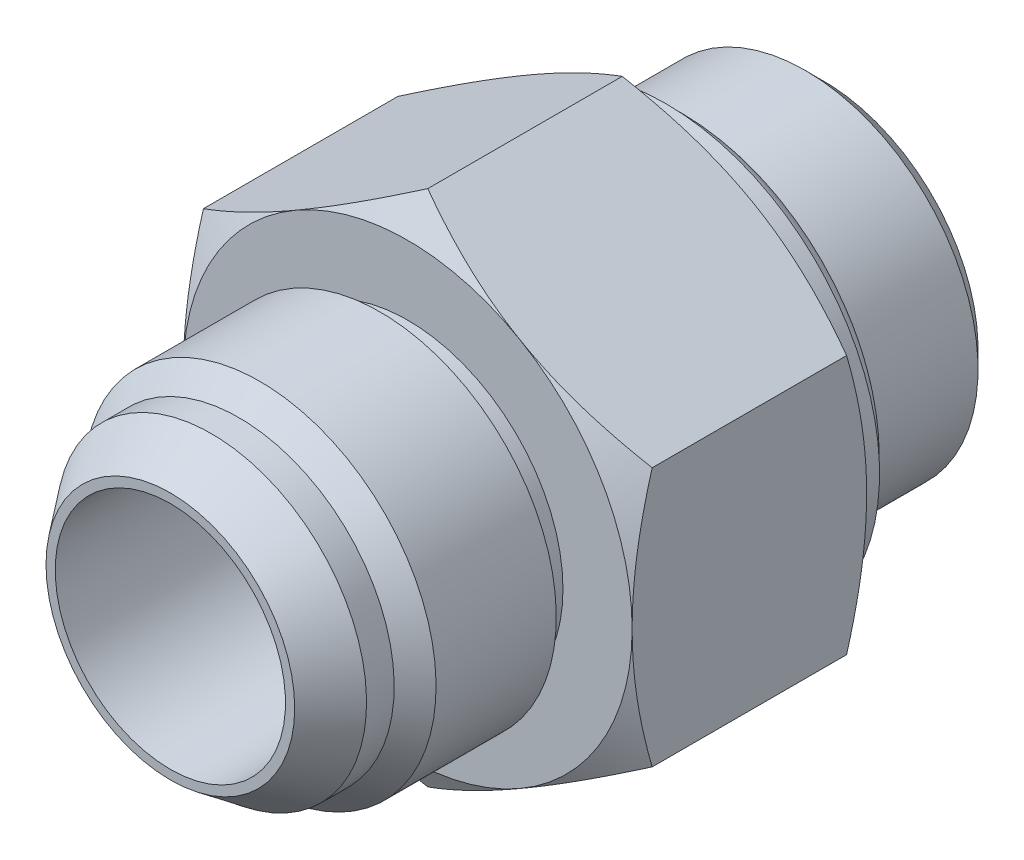
SolidWorks part; units mm, degrees
material "AISI 316 Stainless Steel Sheet (SS)"
ref_plane "Front Plane" through (0, 0, 0) normal (0, 0, 1) x (1, 0, 0)
ref_plane "Top Plane" through (0, 0, 0) normal (0, 1, 0) x (1, 0, 0)
ref_plane "Right Plane" through (0, 0, 0) normal (1, 0, 0) x (0, 0, -1)
sketch "Sketch1" plane through (0, 0, 0) normal (1, 0, 0) x (0, 0, -1)
  line L0 (-25.0031, 0) -> (25.0031, 0) construction
  line L1 (11.1423, 13.2207) -> (11.1423, -13.2207) construction
  line L2 (-6.819, 13.4937) -> (-6.819, -13.4938) construction
  line L3 (11.1423, 13.2207) -> (25.0031, 13.2207) construction
  line L4 (24.8897, 13.4385) -> (26.704, 13.4385) construction
  line L5 (24.8897, 13.4385) -> (25.7969, 11.6959) construction
  line L6 (25.7969, 11.6959) -> (26.704, 13.4385) construction
  line L7 (25.7969, 13.4385) -> (25.7969, 13.2207) construction
  line L8 (25.7969, 11.6959) -> (25.7969, 11.9137) construction
  line L9 (25.6835, 11.9137) -> (25.9103, 11.9137) construction
  line L10 (25.0031, 13.2207) -> (26.5906, 13.2207) construction
  line L11 (26.6473, 13.3296) -> (24.9464, 13.3296) construction
  line L12 (-26.9875, 13.7229) -> (-25.9292, 11.8898)
  line L13 (-26.9875, 13.7229) -> (-24.8708, 13.7229)
  line L14 (-24.8708, 13.7229) -> (-25.9292, 11.8898)
  line L15 (-25.9292, 13.7229) -> (-25.9292, 13.4937) construction
  line L16 (-25.9292, 11.8898) -> (-25.9292, 12.1189) construction
  line L17 (-26.0615, 12.1189) -> (-25.7969, 12.1189) construction
  line L18 (-26.8552, 13.4937) -> (-25.0031, 13.4937) construction
  line L19 (-26.9214, 13.6083) -> (-24.937, 13.6083) construction
  line L20 (11.1423, 17.1869) -> (11.1423, -17.1869) construction
  line L21 (11.1423, -13.2207) -> (25.0031, -13.2207) construction
  point P2 (11.1423, 0)
  point P4 (-6.819, 0)
  point P27 (25.7969, 13.3296)
  point P32 (-17.5948, -13.4937)
  point P33 (18.6531, -13.2207)
  point P40 (-25.9292, 13.6083)
  dimension "Length" = 50.0062
  dimension "PTL" = 13.8608
  dimension "PD" = 26.4414
  dimension "TD" = 26.9875
  dimension "D1" = 55
  dimension "P Pitch" = 1.8143
  dimension "D2" = 0.2268
  dimension "T Pitch" = 2.1167
  dimension "D3" = 0.2646
  dimension "D4" = 18.1841
  dimension "D5" = 34.3738
  dimension "D6" = 7.4083
  dimension "D7" = 6.35
sketch "Sketch2" plane through (0, 0, 0) normal (0, 0, 1) x (1, 0, 0)
  line L0 (0, 13.2207) -> (0, -13.2207) construction
  line L1 (0, 19.8457) -> (-17.1869, 9.9229)
  line L2 (-17.1869, 9.9229) -> (-17.1869, -9.9229)
  line L3 (-17.1869, -9.9229) -> (0, -19.8457)
  line L4 (0, -19.8457) -> (17.1869, -9.9229)
  line L5 (17.1869, -9.9229) -> (17.1869, 9.9229)
  line L6 (17.1869, 9.9229) -> (0, 19.8457)
  circle A0 centre (0, 0) radius 17.1869 construction
extrude "Boss-Extrude1" add sketch "Sketch2" along normal up to vertex (6.819 mm away) from vertex up to point (0, 0, 6.819) starting at point (0, 0, -11.1423)
sketch "Sketch3" plane through (0, 0, 6.819) normal (0, 0, 1) x (1, 0, 0)
  circle A0 centre (0, 0) radius 17.1869 construction
  circle A1 centre (0, 0) radius 17.1869
extrude "Cut-Extrude1" cut sketch "Sketch3" against normal through all draft 60 flip side to cut
sketch "Sketch4" plane through (0, 0, -11.1423) normal (0, 0, -1) x (-1, 0, 0)
  circle A0 centre (0, 0) radius 17.1869 construction
  circle A1 centre (0, 0) radius 17.1869
extrude "Cut-Extrude2" cut sketch "Sketch4" against normal through all draft 60 flip side to cut
sketch "Sketch5" plane through (0, 0, 0) normal (1, 0, 0) x (0, 0, -1)
  line L0 (-25.0031, 0) -> (-25.0031, 9.525)
  line L1 (-25.0031, 9.525) -> (-21.8649, 11.8898)
  line L2 (-21.8649, 11.8898) -> (-19.7483, 11.8898)
  line L3 (-18.1443, 13.4937) -> (-8.9357, 13.4937)
  line L4 (-8.9357, 13.4937) -> (-8.0097, 11.8898)
  line L5 (2.1617, 13.2207) -> (2.1617, 19.8457) construction
  line L6 (23.6424, 13.2207) -> (25.0031, 11.86)
  line L7 (-5.284, 19.8457) -> (9.6073, 19.8457) construction
  line L8 (11.1423, 13.2207) -> (25.0031, 13.2207) construction
  line L9 (25.0031, 11.86) -> (25.0031, 0)
  line L10 (-25.0031, 0) -> (25.0031, 0) construction
  line L11 (23.6424, 13.2207) -> (13.9652, 13.2207)
  line L12 (-8.0097, 11.8898) -> (2.1617, 11.8898)
  line L13 (2.1617, 11.8898) -> (2.1617, 13.2207)
  line L14 (11.1423, 11.6959) -> (13.4102, 11.6959)
  line L15 (-6.819, 13.4937) -> (-6.819, -13.4938) construction
  line L16 (-19.7483, 11.8898) -> (-18.1443, 13.4937)
  line L17 (-25.0031, 0) -> (25.0031, 0) construction
  line L18 (-25.0031, 0) -> (25.0031, 0)
  line L19 (13.4102, 11.6959) -> (13.9652, 13.2207)
  line L20 (11.1423, 11.6959) -> (11.1423, 13.2207)
  line L21 (11.1423, 13.2207) -> (2.1617, 13.2207)
  line L22 (-25.0031, 0) -> (-29.7627, 0) construction
  dimension "D1" = 37
  dimension "D2" = 2.1167
  dimension "D3" = 60
  dimension "D4" = 45
  dimension "D5" = 2.1167
  dimension "D7" = 45
  dimension "D8" = 1.3607
  dimension "D9" = 2.2679
  dimension "D10" = 70
  dimension "D11" = 5.491
  dimension "TOD" = 19.05
revolve "Revolve1" add sketch "Sketch5" angle 360 about L18
sketch "Sketch6" plane through (0, 0, 0) normal (1, 0, 0) x (0, 0, -1)
  line L0 (-25.0031, 8.8194) -> (11.1423, 8.8194)
  line L1 (25.0031, 9.5188) -> (11.1423, 9.5188)
  line L2 (11.1423, 13.2207) -> (11.1423, -13.2207) construction
  line L3 (11.1423, 9.5188) -> (11.1423, 8.8194)
  line L4 (25.0031, -13.2207) -> (25.0031, 13.2207) construction
  line L5 (-25.0031, 9.525) -> (-25.0031, -9.525) construction
  line L6 (-25.0031, 8.8194) -> (-25.0031, 0)
  line L7 (25.0031, 9.5188) -> (25.0031, 0)
  line L8 (25.0031, 0) -> (-25.0031, 0)
  dimension "D1" = 2.1771
  dimension "D2" = 0.7056
revolve "Cut-Revolve1" cut sketch "Sketch6" angle 360 about L8
sketch "Sketch11" plane through (0, 0, 0) normal (1, 0, 0) x (0, 0, -1)
  line L6 (11.1423, 11.6959) -> (11.1423, 16.3633)
  line L8 (11.1423, 16.3633) -> (12.9566, 16.3633)
  line L9 (12.9566, 16.3633) -> (12.9566, 15.6624)
  line L10 (11.1423, 11.6959) -> (12.9566, 11.6959)
  line L11 (12.9566, 12.3967) -> (12.9566, 11.6959)
  arc A0 (12.9566, 12.3967) -> (12.9566, 15.6624) centre (12.9566, 14.0296) ccw
  point P17 (14.5895, 14.0296)
  dimension "D1" = 1.8143
  dimension "D2" = 1.6329
  dimension "D3" = 4.6673
revolve "Revolve2" add sketch "Sketch11" angle 360 about L0
split "Split1" [suppressed] bodies to split 108
sketch "Sketch7" [suppressed] plane through (0, 0, 25.0031) normal (0, 0, 1) x (1, 0, 0)
  circle A0 centre (0, 0) radius 13.4938
  circle A1 centre (0, 0) radius 13.4937 construction
curve "Helix/Spiral1" [suppressed] pitch 2.1167 height 20.3008 turns 9.5909
sketch "Sketch8" [suppressed] plane through (0, 0, 0) normal (1, 0, 0) x (0, 0, -1)
  line L0 (-24.937, 13.6083) -> (-26.9214, 13.6083)
  line L1 (-26.9214, 13.6083) -> (-26.0615, 12.1189)
  line L2 (-26.0615, 12.1189) -> (-25.7969, 12.1189)
  line L3 (-25.7969, 12.1189) -> (-24.937, 13.6083)
sweep "Cut-Sweep1" [suppressed] cut profiles "Sketch8" path "Helix/Spiral1"
sketch "Sketch9" [suppressed] plane through (0, 0, -25.0031) normal (0, 0, -1) x (-1, 0, 0)
  circle A0 centre (0, 0) radius 13.2207 construction
  circle A1 centre (0, 0) radius 13.2207
curve "Helix/Spiral2" [suppressed]
sketch "Sketch10" [suppressed] plane through (0, 0, 0) normal (1, 0, 0) x (0, 0, -1)
  line L2 (25.7969, 11.6959) -> (25.7969, 11.9137) construction
  line L3 (25.7969, 11.6959) -> (26.704, 13.4385) construction
  line L14 (24.8897, 13.4385) -> (26.6473, 13.3296)
  line L15 (24.8897, 13.4385) -> (25.6311, 12.0143)
  line L16 (25.9626, 12.0143) -> (26.6473, 13.3296)
  line L17 (24.8897, 13.4385) -> (25.7969, 11.6959) construction
  arc A0 (25.6311, 12.0143) -> (25.9626, 12.0143) centre (25.7969, 12.1006) ccw
  dimension "D1" = 0.1869
sweep "Cut-Sweep2" [suppressed] cut profiles "Sketch10" path "Helix/Spiral2"
fillet "Fillet1" [suppressed] radius 0.1682
combine bodies "Combine1" [suppressed] operation type add bodies to combine 111 112 119
ref_axis "Center Axis 1" through (0, 0, 22.2913) along (0, 0, -1)
ref_plane "Contact Plane 1" through (0, 0, 6.819) normal (0, 0, 1) x (1, 0, 0)
ref_plane "Contact Plane 2" through (0, 0, -11.1423) normal (0, 0, -1) x (-1, 0, 0)
equation "\"D2@Sketch1\"=\"P Pitch@Sketch1\"/8"
equation "\"D3@Sketch1\"=\"T Pitch@Sketch1\"/8"
equation "\"D5@Sketch1\"=\"PD@Sketch1\"*1.3"
equation "\"D4@Sketch1\"=\"Length@Sketch1\"/2.75"
equation "\"D2@Sketch5\"=\"T Pitch@Sketch1\"*1.0"
equation "\"D5@Sketch5\"=\"T Pitch@Sketch1\"*1"
equation "\"D1@Sketch6\"=\"P Pitch@Sketch1\"*1.2"
equation "\"D2@Sketch6\"=\"T Pitch@Sketch1\"/3"
equation "\"D8@Sketch5\"=\"P Pitch@Sketch1\"*.750"
equation "\"D6@Sketch1\"=\"T Pitch@Sketch1\"*3.5"
equation "\"D7@Sketch1\"=\"P Pitch@Sketch1\"*3.50"
equation "\"D4@Helix/Spiral1\"=\"T Pitch@Sketch1\""
equation "\"D3@Helix/Spiral1\"=\"D4@Sketch1\"+\"T Pitch@Sketch1\""
equation "\"D4@Helix/Spiral2\"=\"P Pitch@Sketch1\""
equation "\"D3@Helix/Spiral2\"=\"PTL@Sketch1\"+\"P Pitch@Sketch1\""
equation "\"D9@Sketch5\"=\"P Pitch@Sketch1\"*1.25"
equation "\"D1@Sketch11\"=\"D9@Sketch5\"*.8"
equation "\"D2@Sketch11\"=\"D1@Sketch11\"*.9"
equation "\"D3@Sketch11\"=\"D11@Sketch5\"*.85"
equation "\"D1@Fillet1\"=\"D1@Sketch10\"*.9"
